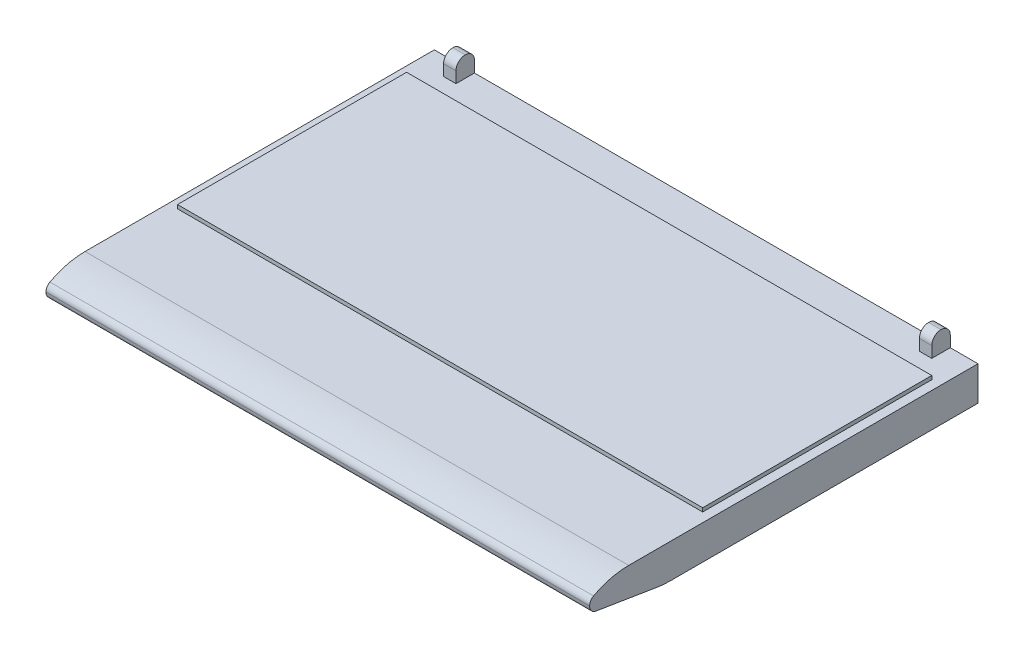
SolidWorks part; units mm, degrees
material "ABS"
ref_plane "Front Plane" through (0, 0, 0) normal (0, 0, 1) x (1, 0, 0)
ref_plane "Top Plane" through (0, 0, 0) normal (0, 1, 0) x (1, 0, 0)
ref_plane "Right Plane" through (0, 0, 0) normal (1, 0, 0) x (0, 0, -1)
sketch "Sketch1" plane through (0, 0, 0) normal (0, 1, 0) x (1, 0, 0)
  line L0 (-147, 0) -> (0, 0) construction
  line L1 (147, 105) -> (-147, 105)
  line L2 (147, 105) -> (147, -105)
  line L3 (147, -105) -> (-147, -105)
  line L4 (-147, 105) -> (-147, -105)
  line L5 (0, 0) -> (0, 105) construction
  dimension "D1" = 210
  dimension "D2" = 294
extrude "Boss-Extrude1" add sketch "Sketch1" along normal blind 18.5
sketch "Sketch2" plane through (147, 0, 0) normal (1, 0, 0) x (0, 0, -1)
  line L0 (-105, 6.5) -> (-65, 0)
  line L1 (-105, 18.5) -> (-105, 0) construction
  line L2 (-105, 0) -> (105, 0) construction
  line L3 (-65, 0) -> (-105, 0)
  line L4 (-105, 0) -> (-105, 6.5)
  dimension "D1" = 40
  dimension "D2" = 12
extrude "Cut-Extrude1" cut sketch "Sketch2" against normal blind 300
chamfer "Chamfer1" distance 6 angle 60 1 edges at (0, 18.5, 105) first distance on face at (0, 12.5, 105)
fillet "Fillet1" radius 40 1 edges at (0, 18.5, 94.6077)
fillet "Fillet2" radius 4 2 edges at (0, 6.5, 105) (0, 12.5, 105)
fillet "Fillet3" radius 50 1 edges at (0, 0, 65)
sketch "Sketch3" plane through (0, 18.5, 0) normal (0, 1, 0) x (1, 0, 0)
  line L0 (147, 105) -> (-147, 105) construction
  line L1 (125.3, 105) -> (132, 105)
  line L2 (125.3, 105) -> (125.3, 95)
  line L3 (125.3, 95) -> (132, 95)
  line L4 (132, 105) -> (132, 95)
  line L5 (0, 105) -> (0, 0) construction
  line L6 (-132, 105) -> (-132, 95)
  line L7 (-125.3, 95) -> (-132, 95)
  line L8 (-125.3, 105) -> (-125.3, 95)
  line L9 (-125.3, 105) -> (-132, 105)
  line L10 (147, -83.8897) -> (147, 105) construction
  dimension "D1" = 6.7
  dimension "D2" = 15
  dimension "D3" = 10
extrude "Boss-Extrude2" add sketch "Sketch3" along normal blind 11
fillet "Fillet4" radius 5 4 edges at (128.65, 29.5, -105) (128.65, 29.5, -95) (-128.65, 29.5, -105) (-128.65, 29.5, -95)
sketch "Sketch4" plane through (0, 18.5, 0) normal (0, 1, 0) x (1, 0, 0)
  line L0 (-147, 105) -> (-147, -83.8897) construction
  line L1 (-142, 85) -> (142, 85)
  line L2 (-142, 85) -> (-142, -38.8897)
  line L3 (-142, -38.8897) -> (142, -38.8897)
  line L4 (142, 85) -> (142, -38.8897)
  line L5 (147, -83.8897) -> (147, 105) construction
  line L6 (-147, -83.8897) -> (147, -83.8897) construction
  line L7 (125.3, 105) -> (-125.3, 105) construction
  dimension "D1" = 5
  dimension "D2" = 5
  dimension "D3" = 45
  dimension "D4" = 20
extrude "Boss-Extrude3" add sketch "Sketch4" along normal blind 2
